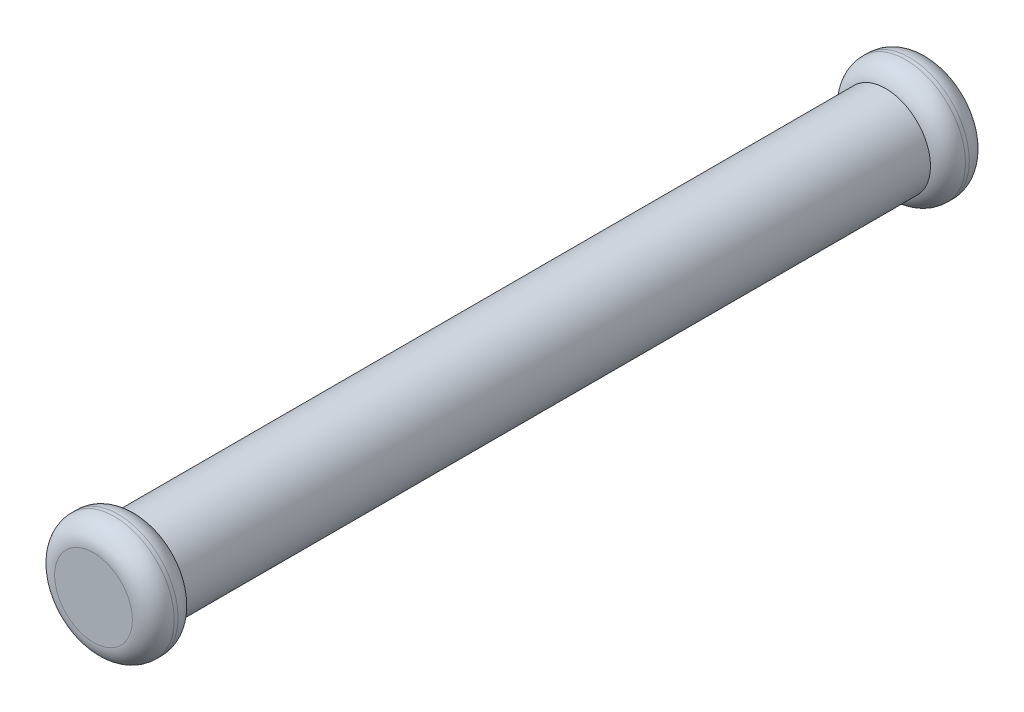
SolidWorks part; units mm, degrees
material "Aço cromo inoxidável"
ref_plane "Plano frontal" through (0, 0, 0) normal (0, 0, 1) x (1, 0, 0)
ref_plane "Plano superior" through (0, 0, 0) normal (0, 1, 0) x (1, 0, 0)
ref_plane "Plano direito" through (0, 0, 0) normal (1, 0, 0) x (0, 0, -1)
sketch "Esboço1" plane through (0, 0, 0) normal (0, 0, 1) x (1, 0, 0)
  circle A0 centre (-16, 2.5) radius 1.5
extrude "Ressalto-extrusão1" add sketch "Esboço1" against normal up to surface (25 mm away)
sketch "Esboço2" plane through (0, 0, 0) normal (0, 0, 1) x (1, 0, 0)
  circle A0 centre (-16, 2.5) radius 2
  dimension "D1" = 4
extrude "Ressalto-extrusão2" add sketch "Esboço2" along normal blind 1.5
extrude "Ressalto-extrusão3" add sketch "Esboço2<2>" against normal blind 1.5 from surface starting at face at (-17.5, 2.5, -25)
sketch "Esboço2<2>" plane through (0, 0, 0) normal (0, 0, 1) x (1, 0, 0) same geometry as "Esboço2"
fillet "Filete1" radius 0.7 4 edges at (-14, 2.5, 0) (-14, 2.5, 1.5) (-18, 2.5, -25) (-18, 2.5, -26.5)
